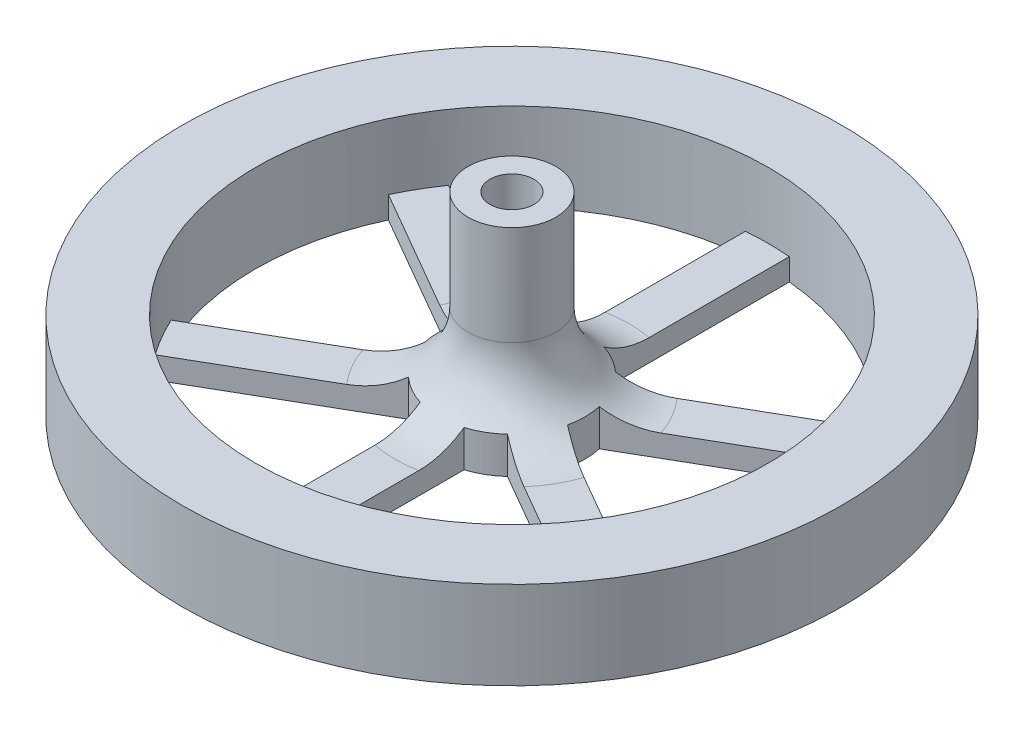
SolidWorks part; units mm, degrees
ref_plane "Front Plane" through (0, 0, 0) normal (0, 0, 1) x (1, 0, 0)
ref_plane "Top Plane" through (0, 0, 0) normal (0, 1, 0) x (1, 0, 0)
ref_plane "Right Plane" through (0, 0, 0) normal (1, 0, 0) x (0, 0, -1)
sketch "Sketch2" plane through (0, 0, 0) normal (0, 1, 0) x (1, 0, 0)
  circle A0 centre (0, 0) radius 45
  circle A1 centre (0, 0) radius 35
  dimension "D1" = 90
  dimension "D2" = 10
extrude "Boss-Extrude1" add sketch "Sketch2" along normal blind 12
sketch "Sketch3" plane through (0, 0, 0) normal (0, -1, 0) x (1, 0, 0)
  line L1 (-3, 40.1148) -> (3, 40.1148)
  line L2 (-3, 40.1148) -> (-3, 9.5394)
  line L4 (3, 40.1148) -> (3, 9.5394)
  arc A0 (-3, 9.5394) -> (3, 9.5394) centre (0, 0) ccw
  point P1 (0, 40.1148)
  dimension "D1" = 20
  dimension "D2" = 6
extrude "Boss-Extrude2" add sketch "Sketch3" against normal blind 3
pattern_circular "CirPattern1" count 6 every 60 about axis through (0, 0, 0) along (0, -1, 0) of "Boss-Extrude2"
sketch "Sketch4" plane through (0, 3, 0) normal (0, 1, 0) x (1, 0, 0)
  circle A0 centre (0, 0) radius 6
  circle A1 centre (0, 0) radius 3
  dimension "D1" = 12
  dimension "D2" = 6
extrude "Boss-Extrude3" add sketch "Sketch4" along normal blind 23.6
fillet "Fillet1" radius 10 1 edges at (0, 3, -6)
